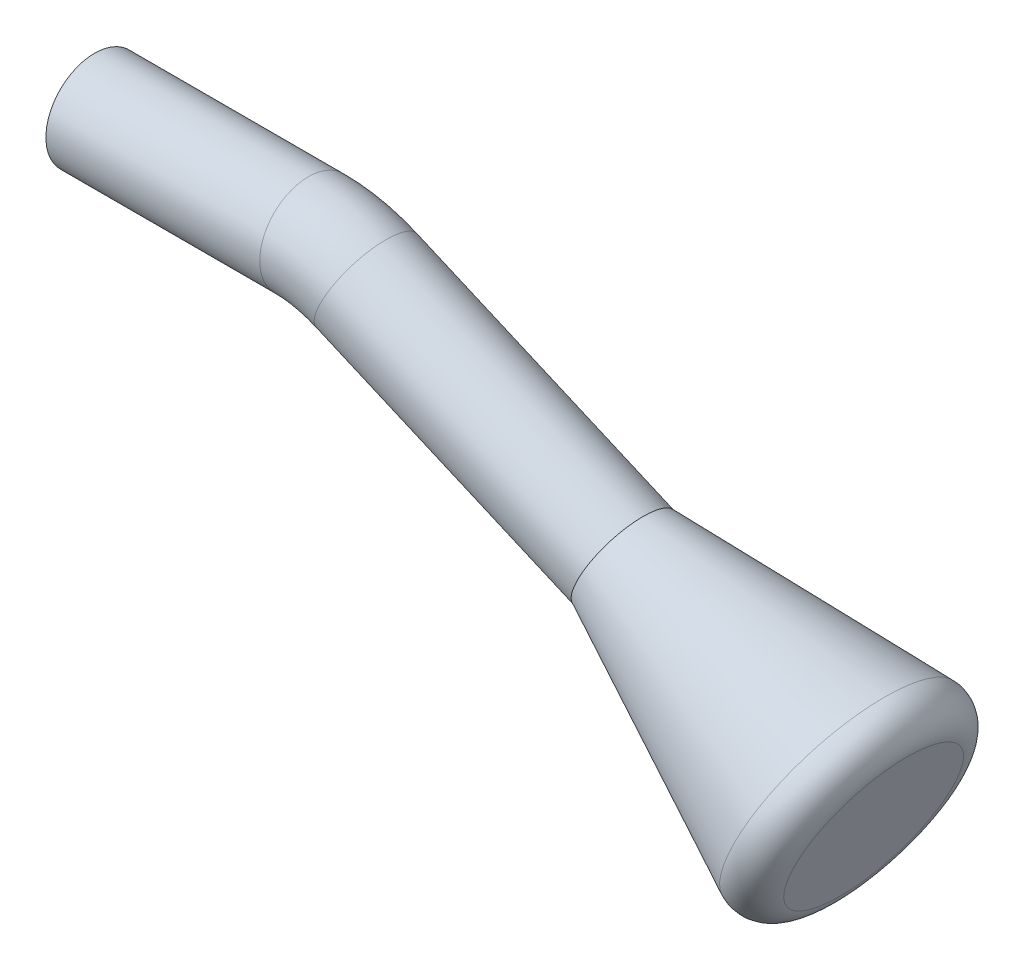
SolidWorks part; units mm, degrees
ref_plane "Спереди" through (0, 0, 0) normal (0, 0, 1) x (1, 0, 0)
ref_plane "Сверху" through (0, 0, 0) normal (0, 1, 0) x (1, 0, 0)
ref_plane "Справа" through (0, 0, 0) normal (1, 0, 0) x (0, 0, -1)
sketch "Эскиз1" plane through (0, 0, 0) normal (0, 0, 1) x (1, 0, 0)
  line L0 (0, 0) -> (21.9586, 0)
  line L1 (27.9151, -1.2334) -> (80, -23.7694)
  line L2 (27.9151, -1.2334) -> (21.9586, -15) construction
  line L3 (21.9586, -15) -> (21.9586, 0) construction
  line L4 (21.9586, 0) -> (27.9151, -1.2334) construction
  line L5 (21.9586, -15) -> (25, -0.3116) construction
  arc A0 (21.9586, 0) -> (27.9151, -1.2334) centre (21.9586, -15) cw
  point P9 (21.9586, 0)
  dimension "D1" = 15
  dimension "D2" = 25
  dimension "D3" = 80
sketch "Эскиз2" plane through (0, 0, 0) normal (1, 0, 0) x (0, 0, -1)
  circle A0 centre (0, 0) radius 5
  dimension "D1" = 10
sweep "По траектории1" add profiles "Эскиз2" path "Эскиз1"
sketch "Эскиз3" plane through (76.0476, -32.9042, 0) normal (0.9178, -0.3971, 0) x (0, 0, -1)
  circle A0 centre (0, 9.9532) radius 12.5
  circle A1 centre (0, 9.9532) radius 5 construction
  point P2 (0, 0)
  dimension "D1" = 25
extrude "Бобышка-Вытянуть1" add sketch "Эскиз3" against normal blind 30 draft 15
fillet "Скругление2" radius 3 1 edges at (84.9638, -12.2972, 0)
